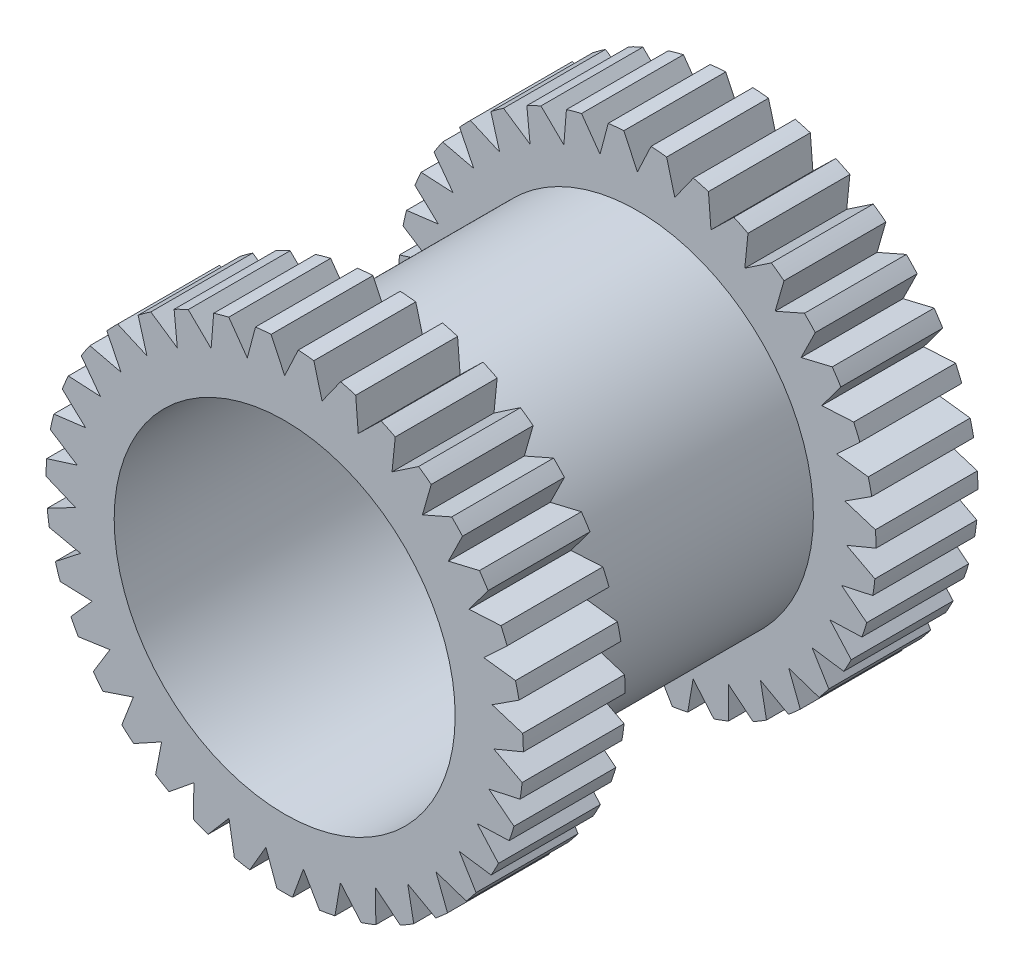
SolidWorks part; units mm, degrees
material "Brass"
ref_plane "Front Plane" through (0, 0, 0) normal (0, 0, 1) x (1, 0, 0)
ref_plane "Top Plane" through (0, 0, 0) normal (0, 1, 0) x (1, 0, 0)
ref_plane "Right Plane" through (0, 0, 0) normal (1, 0, 0) x (0, 0, -1)
sketch "Sketch1" plane through (0, 0, 0) normal (0, 1, 0) x (1, 0, 0)
  line L0 (2.1, 2) -> (0, 2)
  line L1 (0, 2) -> (0, -2)
  line L2 (0, -2) -> (2.1, -2)
  line L3 (2.1, -2) -> (2.1, -1.1034)
  line L4 (2.1, -1.1034) -> (1.5483, -1.1034)
  line L5 (1.5483, -1.1034) -> (1.5483, 1.1034)
  line L6 (1.5483, 1.1034) -> (2.1, 1.1034)
  line L7 (2.1, 1.1034) -> (2.1, 2)
  line L8 (0, 2) -> (0, -2) construction
  dimension "D1" = 4
  dimension "D2" = 2.1
revolve "Revolve1" add sketch "Sketch1" angle 360 about L8 reverse direction yes
sketch "Sketch2" plane through (0, 0, -2) normal (0, 0, -1) x (-1, 0, 0)
  line L0 (0.673, -1.9892) -> (0.49, -1.7755)
  line L1 (0.49, -1.7755) -> (0.4425, -2.0528)
  arc A0 (0.4425, -2.0528) -> (0.673, -1.9892) centre (0, 0) ccw
extrude "Cut-Extrude1" cut sketch "Sketch2" against normal blind 0.65
sketch "Sketch3" plane through (0, 0, -2) normal (0, 0, -1) x (-1, 0, 0)
  line L0 (0.307, -2.0774) -> (0.1651, -1.8345)
  line L1 (0.1651, -1.8345) -> (0.0689, -2.0989)
  arc A0 (0.0689, -2.0989) -> (0.307, -2.0774) centre (0, 0) ccw
extrude "Cut-Extrude2" cut sketch "Sketch3" against normal blind 0.65
sketch "Sketch4" plane through (0, 0, -2) normal (0, 0, -1) x (-1, 0, 0)
  line L0 (-0.0689, -2.0989) -> (-0.1651, -1.8345)
  line L1 (-0.1651, -1.8345) -> (-0.307, -2.0774)
  arc A0 (-0.307, -2.0774) -> (-0.0689, -2.0989) centre (0, 0) ccw
extrude "Cut-Extrude3" cut sketch "Sketch4" against normal blind 0.65
sketch "Sketch5" plane through (0, 0, -2) normal (0, 0, -1) x (-1, 0, 0)
  line L0 (-0.4425, -2.0528) -> (-0.49, -1.7755)
  line L1 (-0.49, -1.7755) -> (-0.673, -1.9892)
  arc A0 (-0.673, -1.9892) -> (-0.4425, -2.0528) centre (0, 0) ccw
extrude "Cut-Extrude4" cut sketch "Sketch5" against normal blind 0.65
sketch "Sketch6" plane through (0, 0, -2) normal (0, 0, -1) x (-1, 0, 0)
  line L0 (-0.802, -1.9408) -> (-0.7992, -1.6595)
  line L1 (-0.7992, -1.6595) -> (-1.0174, -1.8371)
  arc A0 (-1.0174, -1.8371) -> (-0.802, -1.9408) centre (0, 0) ccw
extrude "Cut-Extrude5" cut sketch "Sketch6" against normal blind 0.65
sketch "Sketch7" plane through (0, 0, -2) normal (0, 0, -1) x (-1, 0, 0)
  line L0 (-1.1356, -1.7664) -> (-1.0826, -1.4901)
  line L1 (-1.0826, -1.4901) -> (-1.3291, -1.6259)
  arc A0 (-1.3291, -1.6259) -> (-1.1356, -1.7664) centre (0, 0) ccw
extrude "Cut-Extrude6" cut sketch "Sketch7" against normal blind 0.65
sketch "Sketch8" plane through (0, 0, -2) normal (0, 0, -1) x (-1, 0, 0)
  line L0 (-1.4328, -1.5353) -> (-1.3313, -1.2729)
  line L1 (-1.3313, -1.2729) -> (-1.598, -1.3625)
  arc A0 (-1.598, -1.3625) -> (-1.4328, -1.5353) centre (0, 0) ccw
extrude "Cut-Extrude7" cut sketch "Sketch8" against normal blind 0.65
sketch "Sketch9" plane through (0, 0, -2) normal (0, 0, -1) x (-1, 0, 0)
  line L0 (-1.6839, -1.2548) -> (-1.5372, -1.0147)
  line L1 (-1.5372, -1.0147) -> (-1.8156, -1.0552)
  arc A0 (-1.8156, -1.0552) -> (-1.6839, -1.2548) centre (0, 0) ccw
extrude "Cut-Extrude8" cut sketch "Sketch9" against normal blind 0.65
sketch "Sketch10" plane through (0, 0, -2) normal (0, 0, -1) x (-1, 0, 0)
  line L0 (-1.8809, -0.9339) -> (-1.6937, -0.7239)
  line L1 (-1.6937, -0.7239) -> (-1.9749, -0.7141)
  arc A0 (-1.9749, -0.7141) -> (-1.8809, -0.9339) centre (0, 0) ccw
extrude "Cut-Extrude9" cut sketch "Sketch10" against normal blind 0.65
sketch "Sketch11" plane through (0, 0, -2) normal (0, 0, -1) x (-1, 0, 0)
  line L0 (-2.0174, -0.5831) -> (-1.7957, -0.4099)
  line L1 (-1.7957, -0.4099) -> (-2.0706, -0.35)
  arc A0 (-2.0706, -0.35) -> (-2.0174, -0.5831) centre (0, 0) ccw
extrude "Cut-Extrude10" cut sketch "Sketch11" against normal blind 0.65
sketch "Sketch12" plane through (0, 0, -2) normal (0, 0, -1) x (-1, 0, 0)
  line L0 (-2.0891, -0.2135) -> (-1.84, -0.0826)
  line L1 (-1.84, -0.0826) -> (-2.0998, 0.0254)
  arc A0 (-2.0998, 0.0254) -> (-2.0891, -0.2135) centre (0, 0) ccw
extrude "Cut-Extrude11" cut sketch "Sketch12" against normal blind 0.65
sketch "Sketch13" plane through (0, 0, -2) normal (0, 0, -1) x (-1, 0, 0)
  line L0 (-2.0937, 0.163) -> (-1.8252, 0.2472)
  line L1 (-1.8252, 0.2472) -> (-2.0616, 0.3999)
  arc A0 (-2.0616, 0.3999) -> (-2.0937, 0.163) centre (0, 0) ccw
extrude "Cut-Extrude12" cut sketch "Sketch13" against normal blind 0.65
sketch "Sketch14" plane through (0, 0, -2) normal (0, 0, -1) x (-1, 0, 0)
  line L0 (-2.0309, 0.5342) -> (-1.7517, 0.5692)
  line L1 (-1.7517, 0.5692) -> (-1.957, 0.7616)
  arc A0 (-1.957, 0.7616) -> (-2.0309, 0.5342) centre (0, 0) ccw
extrude "Cut-Extrude13" cut sketch "Sketch14" against normal blind 0.65
sketch "Sketch15" plane through (0, 0, -2) normal (0, 0, -1) x (-1, 0, 0)
  line L0 (-1.9029, 0.8882) -> (-1.622, 0.8728)
  line L1 (-1.622, 0.8728) -> (-1.7896, 1.0988)
  arc A0 (-1.7896, 1.0988) -> (-1.9029, 0.8882) centre (0, 0) ccw
extrude "Cut-Extrude14" cut sketch "Sketch15" against normal blind 0.65
sketch "Sketch16" plane through (0, 0, -2) normal (0, 0, -1) x (-1, 0, 0)
  line L0 (-1.7137, 1.2137) -> (-1.44, 1.1484)
  line L1 (-1.44, 1.1484) -> (-1.5646, 1.4007)
  arc A0 (-1.5646, 1.4007) -> (-1.7137, 1.2137) centre (0, 0) ccw
extrude "Cut-Extrude15" cut sketch "Sketch16" against normal blind 0.65
sketch "Sketch17" plane through (0, 0, -2) normal (0, 0, -1) x (-1, 0, 0)
  line L0 (-1.4695, 1.5002) -> (-1.2118, 1.3871)
  line L1 (-1.2118, 1.3871) -> (-1.2894, 1.6575)
  arc A0 (-1.2894, 1.6575) -> (-1.4695, 1.5002) centre (0, 0) ccw
extrude "Cut-Extrude16" cut sketch "Sketch17" against normal blind 0.65
sketch "Sketch18" plane through (0, 0, -2) normal (0, 0, -1) x (-1, 0, 0)
  line L0 (-1.178, 1.7385) -> (-0.9447, 1.5812)
  line L1 (-0.9447, 1.5812) -> (-0.9727, 1.8611)
  arc A0 (-0.9727, 1.8611) -> (-1.178, 1.7385) centre (0, 0) ccw
extrude "Cut-Extrude17" cut sketch "Sketch18" against normal blind 0.65
sketch "Sketch19" plane through (0, 0, -2) normal (0, 0, -1) x (-1, 0, 0)
  line L0 (-0.8486, 1.9209) -> (-0.6472, 1.7244)
  line L1 (-0.6472, 1.7244) -> (-0.6248, 2.0049)
  arc A0 (-0.6248, 2.0049) -> (-0.8486, 1.9209) centre (0, 0) ccw
extrude "Cut-Extrude18" cut sketch "Sketch19" against normal blind 0.65
sketch "Sketch20" plane through (0, 0, -2) normal (0, 0, -1) x (-1, 0, 0)
  line L0 (-0.492, 2.0416) -> (-0.3289, 1.8123)
  line L1 (-0.3289, 1.8123) -> (-0.2567, 2.0842)
  arc A0 (-0.2567, 2.0842) -> (-0.492, 2.0416) centre (0, 0) ccw
extrude "Cut-Extrude19" cut sketch "Sketch20" against normal blind 0.65
sketch "Sketch21" plane through (0, 0, -2) normal (0, 0, -1) x (-1, 0, 0)
  line L0 (-0.1195, 2.0966) -> (0, 1.8419)
  line L1 (0, 1.8419) -> (0.1195, 2.0966)
  arc A0 (0.1195, 2.0966) -> (-0.1195, 2.0966) centre (0, 0) ccw
extrude "Cut-Extrude20" cut sketch "Sketch21" against normal blind 0.65
sketch "Sketch22" plane through (0, 0, -2) normal (0, 0, -1) x (-1, 0, 0)
  line L0 (0.2567, 2.0842) -> (0.3289, 1.8123)
  line L1 (0.3289, 1.8123) -> (0.492, 2.0416)
  arc A0 (0.492, 2.0416) -> (0.2567, 2.0842) centre (0, 0) ccw
extrude "Cut-Extrude21" cut sketch "Sketch22" against normal blind 0.65
sketch "Sketch23" plane through (0, 0, -2) normal (0, 0, -1) x (-1, 0, 0)
  line L0 (0.6248, 2.0049) -> (0.6472, 1.7244)
  line L1 (0.6472, 1.7244) -> (0.8486, 1.9209)
  arc A0 (0.8486, 1.9209) -> (0.6248, 2.0049) centre (0, 0) ccw
extrude "Cut-Extrude22" cut sketch "Sketch23" against normal blind 0.65
sketch "Sketch24" plane through (0, 0, -2) normal (0, 0, -1) x (-1, 0, 0)
  line L0 (0.9727, 1.8611) -> (0.9447, 1.5812)
  line L1 (0.9447, 1.5812) -> (1.178, 1.7385)
  arc A0 (1.178, 1.7385) -> (0.9727, 1.8611) centre (0, 0) ccw
extrude "Cut-Extrude23" cut sketch "Sketch24" against normal blind 0.65
sketch "Sketch25" plane through (0, 0, -2) normal (0, 0, -1) x (-1, 0, 0)
  line L0 (1.2894, 1.6575) -> (1.2118, 1.3871)
  line L1 (1.2118, 1.3871) -> (1.4695, 1.5002)
  arc A0 (1.4695, 1.5002) -> (1.2894, 1.6575) centre (0, 0) ccw
extrude "Cut-Extrude24" cut sketch "Sketch25" against normal blind 0.65
sketch "Sketch26" plane through (0, 0, -2) normal (0, 0, -1) x (-1, 0, 0)
  line L0 (1.5646, 1.4007) -> (1.44, 1.1484)
  line L1 (1.44, 1.1484) -> (1.7137, 1.2137)
  arc A0 (1.7137, 1.2137) -> (1.5646, 1.4007) centre (0, 0) ccw
extrude "Cut-Extrude25" cut sketch "Sketch26" against normal blind 0.65
sketch "Sketch27" plane through (0, 0, -2) normal (0, 0, -1) x (-1, 0, 0)
  line L0 (1.7896, 1.0988) -> (1.622, 0.8728)
  line L1 (1.622, 0.8728) -> (1.9029, 0.8882)
  arc A0 (1.9029, 0.8882) -> (1.7896, 1.0988) centre (0, 0) ccw
extrude "Cut-Extrude26" cut sketch "Sketch27" against normal blind 0.65
sketch "Sketch28" plane through (0, 0, -2) normal (0, 0, -1) x (-1, 0, 0)
  line L0 (1.957, 0.7616) -> (1.7517, 0.5692)
  line L1 (1.7517, 0.5692) -> (2.0309, 0.5342)
  arc A0 (2.0309, 0.5342) -> (1.957, 0.7616) centre (0, 0) ccw
extrude "Cut-Extrude27" cut sketch "Sketch28" against normal blind 0.65
sketch "Sketch29" plane through (0, 0, -2) normal (0, 0, -1) x (-1, 0, 0)
  line L0 (2.0616, 0.3999) -> (1.8252, 0.2472)
  line L1 (1.8252, 0.2472) -> (2.0937, 0.163)
  arc A0 (2.0937, 0.163) -> (2.0616, 0.3999) centre (0, 0) ccw
extrude "Cut-Extrude28" cut sketch "Sketch29" against normal blind 0.65
sketch "Sketch30" plane through (0, 0, -2) normal (0, 0, -1) x (-1, 0, 0)
  line L0 (2.0998, 0.0254) -> (1.84, -0.0826)
  line L1 (1.84, -0.0826) -> (2.0891, -0.2135)
  arc A0 (2.0891, -0.2135) -> (2.0998, 0.0254) centre (0, 0) ccw
extrude "Cut-Extrude29" cut sketch "Sketch30" against normal blind 0.65
sketch "Sketch31" plane through (0, 0, -2) normal (0, 0, -1) x (-1, 0, 0)
  line L0 (2.0706, -0.35) -> (1.7957, -0.4099)
  line L1 (1.7957, -0.4099) -> (2.0174, -0.5831)
  arc A0 (2.0174, -0.5831) -> (2.0706, -0.35) centre (0, 0) ccw
extrude "Cut-Extrude30" cut sketch "Sketch31" against normal blind 0.65
sketch "Sketch32" plane through (0, 0, -2) normal (0, 0, -1) x (-1, 0, 0)
  line L0 (1.9749, -0.7141) -> (1.6937, -0.7239)
  line L1 (1.6937, -0.7239) -> (1.8809, -0.9339)
  arc A0 (1.8809, -0.9339) -> (1.9749, -0.7141) centre (0, 0) ccw
extrude "Cut-Extrude31" cut sketch "Sketch32" against normal blind 0.65
sketch "Sketch33" plane through (0, 0, -2) normal (0, 0, -1) x (-1, 0, 0)
  line L0 (1.8156, -1.0552) -> (1.5372, -1.0147)
  line L1 (1.5372, -1.0147) -> (1.6839, -1.2548)
  arc A0 (1.6839, -1.2548) -> (1.8156, -1.0552) centre (0, 0) ccw
extrude "Cut-Extrude32" cut sketch "Sketch33" against normal blind 0.65
sketch "Sketch34" plane through (0, 0, -2) normal (0, 0, -1) x (-1, 0, 0)
  line L0 (1.598, -1.3625) -> (1.3313, -1.2729)
  line L1 (1.3313, -1.2729) -> (1.4328, -1.5353)
  arc A0 (1.4328, -1.5353) -> (1.598, -1.3625) centre (0, 0) ccw
extrude "Cut-Extrude33" cut sketch "Sketch34" against normal blind 0.65
sketch "Sketch35" plane through (0, 0, -2) normal (0, 0, -1) x (-1, 0, 0)
  line L0 (1.3291, -1.6259) -> (1.0826, -1.4901)
  line L1 (1.0826, -1.4901) -> (1.1356, -1.7664)
  arc A0 (1.1356, -1.7664) -> (1.3291, -1.6259) centre (0, 0) ccw
extrude "Cut-Extrude34" cut sketch "Sketch35" against normal blind 0.65
sketch "Sketch36" plane through (0, 0, -2) normal (0, 0, -1) x (-1, 0, 0)
  line L0 (1.0174, -1.8371) -> (0.7992, -1.6595)
  line L1 (0.7992, -1.6595) -> (0.802, -1.9408)
  arc A0 (0.802, -1.9408) -> (1.0174, -1.8371) centre (0, 0) ccw
extrude "Cut-Extrude35" cut sketch "Sketch36" against normal blind 0.65
sketch "Sketch37" plane through (0, 0, 2) normal (0, 0, 1) x (1, 0, 0)
  line L0 (-0.4425, -2.0528) -> (-0.49, -1.7755)
  line L1 (-0.49, -1.7755) -> (-0.673, -1.9892)
  arc A0 (-0.673, -1.9892) -> (-0.4425, -2.0528) centre (0, 0) ccw
extrude "Cut-Extrude36" cut sketch "Sketch37" against normal blind 0.65
sketch "Sketch38" plane through (0, 0, 2) normal (0, 0, 1) x (1, 0, 0)
  line L0 (-0.802, -1.9408) -> (-0.7992, -1.6595)
  line L1 (-0.7992, -1.6595) -> (-1.0174, -1.8371)
  arc A0 (-1.0174, -1.8371) -> (-0.802, -1.9408) centre (0, 0) ccw
extrude "Cut-Extrude37" cut sketch "Sketch38" against normal blind 0.65
sketch "Sketch39" plane through (0, 0, 2) normal (0, 0, 1) x (1, 0, 0)
  line L0 (-1.1356, -1.7664) -> (-1.0826, -1.4901)
  line L1 (-1.0826, -1.4901) -> (-1.3291, -1.6259)
  arc A0 (-1.3291, -1.6259) -> (-1.1356, -1.7664) centre (0, 0) ccw
extrude "Cut-Extrude38" cut sketch "Sketch39" against normal blind 0.65
sketch "Sketch40" plane through (0, 0, 2) normal (0, 0, 1) x (1, 0, 0)
  line L0 (-1.4328, -1.5353) -> (-1.3313, -1.2729)
  line L1 (-1.3313, -1.2729) -> (-1.598, -1.3625)
  arc A0 (-1.598, -1.3625) -> (-1.4328, -1.5353) centre (0, 0) ccw
extrude "Cut-Extrude39" cut sketch "Sketch40" against normal blind 0.65
sketch "Sketch41" plane through (0, 0, 2) normal (0, 0, 1) x (1, 0, 0)
  line L0 (-1.6839, -1.2548) -> (-1.5372, -1.0147)
  line L1 (-1.5372, -1.0147) -> (-1.8156, -1.0552)
  arc A0 (-1.8156, -1.0552) -> (-1.6839, -1.2548) centre (0, 0) ccw
extrude "Cut-Extrude40" cut sketch "Sketch41" against normal blind 0.65
sketch "Sketch42" plane through (0, 0, 2) normal (0, 0, 1) x (1, 0, 0)
  line L0 (-1.8809, -0.9339) -> (-1.6937, -0.7239)
  line L1 (-1.6937, -0.7239) -> (-1.9749, -0.7141)
  arc A0 (-1.9749, -0.7141) -> (-1.8809, -0.9339) centre (0, 0) ccw
extrude "Cut-Extrude41" cut sketch "Sketch42" against normal blind 0.65
sketch "Sketch43" plane through (0, 0, 2) normal (0, 0, 1) x (1, 0, 0)
  line L0 (-2.0174, -0.5831) -> (-1.7957, -0.4099)
  line L1 (-1.7957, -0.4099) -> (-2.0706, -0.35)
  arc A0 (-2.0706, -0.35) -> (-2.0174, -0.5831) centre (0, 0) ccw
extrude "Cut-Extrude42" cut sketch "Sketch43" against normal blind 0.65
sketch "Sketch44" plane through (0, 0, 2) normal (0, 0, 1) x (1, 0, 0)
  line L0 (-2.0891, -0.2135) -> (-1.84, -0.0826)
  line L1 (-1.84, -0.0826) -> (-2.0998, 0.0254)
  arc A0 (-2.0998, 0.0254) -> (-2.0891, -0.2135) centre (0, 0) ccw
extrude "Cut-Extrude43" cut sketch "Sketch44" against normal blind 0.65
sketch "Sketch45" plane through (0, 0, 2) normal (0, 0, 1) x (1, 0, 0)
  line L0 (-2.0937, 0.163) -> (-1.8252, 0.2472)
  line L1 (-1.8252, 0.2472) -> (-2.0616, 0.3999)
  arc A0 (-2.0616, 0.3999) -> (-2.0937, 0.163) centre (0, 0) ccw
extrude "Cut-Extrude44" cut sketch "Sketch45" against normal blind 0.65
sketch "Sketch46" plane through (0, 0, 2) normal (0, 0, 1) x (1, 0, 0)
  line L0 (-2.0309, 0.5342) -> (-1.7517, 0.5692)
  line L1 (-1.7517, 0.5692) -> (-1.957, 0.7616)
  arc A0 (-1.957, 0.7616) -> (-2.0309, 0.5342) centre (0, 0) ccw
extrude "Cut-Extrude45" cut sketch "Sketch46" against normal blind 0.65
sketch "Sketch47" plane through (0, 0, 2) normal (0, 0, 1) x (1, 0, 0)
  line L0 (-1.9029, 0.8882) -> (-1.622, 0.8728)
  line L1 (-1.622, 0.8728) -> (-1.7896, 1.0988)
  arc A0 (-1.7896, 1.0988) -> (-1.9029, 0.8882) centre (0, 0) ccw
extrude "Cut-Extrude46" cut sketch "Sketch47" against normal blind 0.65
sketch "Sketch48" plane through (0, 0, 2) normal (0, 0, 1) x (1, 0, 0)
  line L0 (-1.7137, 1.2137) -> (-1.44, 1.1484)
  line L1 (-1.44, 1.1484) -> (-1.5646, 1.4007)
  arc A0 (-1.5646, 1.4007) -> (-1.7137, 1.2137) centre (0, 0) ccw
extrude "Cut-Extrude47" cut sketch "Sketch48" against normal blind 0.65
sketch "Sketch49" plane through (0, 0, 2) normal (0, 0, 1) x (1, 0, 0)
  line L0 (-1.4695, 1.5002) -> (-1.2118, 1.3871)
  line L1 (-1.2118, 1.3871) -> (-1.2894, 1.6575)
  arc A0 (-1.2894, 1.6575) -> (-1.4695, 1.5002) centre (0, 0) ccw
extrude "Cut-Extrude48" cut sketch "Sketch49" against normal blind 0.65
sketch "Sketch50" plane through (0, 0, 2) normal (0, 0, 1) x (1, 0, 0)
  line L0 (-1.178, 1.7385) -> (-0.9447, 1.5812)
  line L1 (-0.9447, 1.5812) -> (-0.9727, 1.8611)
  arc A0 (-0.9727, 1.8611) -> (-1.178, 1.7385) centre (0, 0) ccw
extrude "Cut-Extrude49" cut sketch "Sketch50" against normal blind 0.65
sketch "Sketch51" plane through (0, 0, 2) normal (0, 0, 1) x (1, 0, 0)
  line L0 (-0.8486, 1.9209) -> (-0.6472, 1.7244)
  line L1 (-0.6472, 1.7244) -> (-0.6248, 2.0049)
  arc A0 (-0.6248, 2.0049) -> (-0.8486, 1.9209) centre (0, 0) ccw
extrude "Cut-Extrude50" cut sketch "Sketch51" against normal blind 0.65
sketch "Sketch52" plane through (0, 0, 2) normal (0, 0, 1) x (1, 0, 0)
  line L0 (-0.492, 2.0416) -> (-0.3289, 1.8123)
  line L1 (-0.3289, 1.8123) -> (-0.2567, 2.0842)
  arc A0 (-0.2567, 2.0842) -> (-0.492, 2.0416) centre (0, 0) ccw
extrude "Cut-Extrude51" cut sketch "Sketch52" against normal blind 0.65
sketch "Sketch53" plane through (0, 0, 2) normal (0, 0, 1) x (1, 0, 0)
  line L0 (-0.1195, 2.0966) -> (0, 1.8419)
  line L1 (0, 1.8419) -> (0.1195, 2.0966)
  arc A0 (0.1195, 2.0966) -> (-0.1195, 2.0966) centre (0, 0) ccw
extrude "Cut-Extrude52" cut sketch "Sketch53" against normal blind 0.65
sketch "Sketch54" plane through (0, 0, 2) normal (0, 0, 1) x (1, 0, 0)
  line L0 (0.2567, 2.0842) -> (0.3289, 1.8123)
  line L1 (0.3289, 1.8123) -> (0.492, 2.0416)
  arc A0 (0.492, 2.0416) -> (0.2567, 2.0842) centre (0, 0) ccw
extrude "Cut-Extrude53" cut sketch "Sketch54" against normal blind 0.65
sketch "Sketch55" plane through (0, 0, 2) normal (0, 0, 1) x (1, 0, 0)
  line L0 (0.6248, 2.0049) -> (0.6472, 1.7244)
  line L1 (0.6472, 1.7244) -> (0.8486, 1.9209)
  arc A0 (0.8486, 1.9209) -> (0.6248, 2.0049) centre (0, 0) ccw
extrude "Cut-Extrude54" cut sketch "Sketch55" against normal blind 0.65
sketch "Sketch56" plane through (0, 0, 2) normal (0, 0, 1) x (1, 0, 0)
  line L0 (0.9727, 1.8611) -> (0.9447, 1.5812)
  line L1 (0.9447, 1.5812) -> (1.178, 1.7385)
  arc A0 (1.178, 1.7385) -> (0.9727, 1.8611) centre (0, 0) ccw
extrude "Cut-Extrude55" cut sketch "Sketch56" against normal blind 0.65
sketch "Sketch57" plane through (0, 0, 2) normal (0, 0, 1) x (1, 0, 0)
  line L0 (1.2894, 1.6575) -> (1.2118, 1.3871)
  line L1 (1.2118, 1.3871) -> (1.4695, 1.5002)
  arc A0 (1.4695, 1.5002) -> (1.2894, 1.6575) centre (0, 0) ccw
extrude "Cut-Extrude56" cut sketch "Sketch57" against normal blind 0.65
sketch "Sketch58" plane through (0, 0, 2) normal (0, 0, 1) x (1, 0, 0)
  line L0 (1.5646, 1.4007) -> (1.44, 1.1484)
  line L1 (1.44, 1.1484) -> (1.7137, 1.2137)
  arc A0 (1.7137, 1.2137) -> (1.5646, 1.4007) centre (0, 0) ccw
extrude "Cut-Extrude57" cut sketch "Sketch58" against normal blind 0.65
sketch "Sketch59" plane through (0, 0, 2) normal (0, 0, 1) x (1, 0, 0)
  line L0 (1.7896, 1.0988) -> (1.622, 0.8728)
  line L1 (1.622, 0.8728) -> (1.9029, 0.8882)
  arc A0 (1.9029, 0.8882) -> (1.7896, 1.0988) centre (0, 0) ccw
extrude "Cut-Extrude58" cut sketch "Sketch59" against normal blind 0.65
sketch "Sketch60" plane through (0, 0, 2) normal (0, 0, 1) x (1, 0, 0)
  line L0 (1.957, 0.7616) -> (1.7517, 0.5692)
  line L1 (1.7517, 0.5692) -> (2.0309, 0.5342)
  arc A0 (2.0309, 0.5342) -> (1.957, 0.7616) centre (0, 0) ccw
extrude "Cut-Extrude59" cut sketch "Sketch60" against normal blind 0.65
sketch "Sketch61" plane through (0, 0, 2) normal (0, 0, 1) x (1, 0, 0)
  line L0 (2.0616, 0.3999) -> (1.8252, 0.2472)
  line L1 (1.8252, 0.2472) -> (2.0937, 0.163)
  arc A0 (2.0937, 0.163) -> (2.0616, 0.3999) centre (0, 0) ccw
extrude "Cut-Extrude60" cut sketch "Sketch61" against normal blind 0.65
sketch "Sketch62" plane through (0, 0, 2) normal (0, 0, 1) x (1, 0, 0)
  line L0 (2.0998, 0.0254) -> (1.84, -0.0826)
  line L1 (1.84, -0.0826) -> (2.0891, -0.2135)
  arc A0 (2.0891, -0.2135) -> (2.0998, 0.0254) centre (0, 0) ccw
extrude "Cut-Extrude61" cut sketch "Sketch62" against normal blind 0.65
sketch "Sketch63" plane through (0, 0, 2) normal (0, 0, 1) x (1, 0, 0)
  line L0 (2.0706, -0.35) -> (1.7957, -0.4099)
  line L1 (1.7957, -0.4099) -> (2.0174, -0.5831)
  arc A0 (2.0174, -0.5831) -> (2.0706, -0.35) centre (0, 0) ccw
extrude "Cut-Extrude62" cut sketch "Sketch63" against normal blind 0.65
sketch "Sketch64" plane through (0, 0, 2) normal (0, 0, 1) x (1, 0, 0)
  line L0 (1.9749, -0.7141) -> (1.6937, -0.7239)
  line L1 (1.6937, -0.7239) -> (1.8809, -0.9339)
  arc A0 (1.8809, -0.9339) -> (1.9749, -0.7141) centre (0, 0) ccw
extrude "Cut-Extrude63" cut sketch "Sketch64" against normal blind 0.65
sketch "Sketch65" plane through (0, 0, 2) normal (0, 0, 1) x (1, 0, 0)
  line L0 (1.8156, -1.0552) -> (1.5372, -1.0147)
  line L1 (1.5372, -1.0147) -> (1.6839, -1.2548)
  arc A0 (1.6839, -1.2548) -> (1.8156, -1.0552) centre (0, 0) ccw
extrude "Cut-Extrude64" cut sketch "Sketch65" against normal blind 0.65
sketch "Sketch66" plane through (0, 0, 2) normal (0, 0, 1) x (1, 0, 0)
  line L0 (1.598, -1.3625) -> (1.3313, -1.2729)
  line L1 (1.3313, -1.2729) -> (1.4328, -1.5353)
  arc A0 (1.4328, -1.5353) -> (1.598, -1.3625) centre (0, 0) ccw
extrude "Cut-Extrude65" cut sketch "Sketch66" against normal blind 0.65
sketch "Sketch67" plane through (0, 0, 2) normal (0, 0, 1) x (1, 0, 0)
  line L0 (1.3291, -1.6259) -> (1.0826, -1.4901)
  line L1 (1.0826, -1.4901) -> (1.1356, -1.7664)
  arc A0 (1.1356, -1.7664) -> (1.3291, -1.6259) centre (0, 0) ccw
extrude "Cut-Extrude66" cut sketch "Sketch67" against normal blind 0.65
sketch "Sketch68" plane through (0, 0, 2) normal (0, 0, 1) x (1, 0, 0)
  line L0 (1.0174, -1.8371) -> (0.7992, -1.6595)
  line L1 (0.7992, -1.6595) -> (0.802, -1.9408)
  arc A0 (0.802, -1.9408) -> (1.0174, -1.8371) centre (0, 0) ccw
extrude "Cut-Extrude67" cut sketch "Sketch68" against normal blind 0.65
sketch "Sketch69" plane through (0, 0, 2) normal (0, 0, 1) x (1, 0, 0)
  line L0 (0.673, -1.9892) -> (0.49, -1.7755)
  line L1 (0.49, -1.7755) -> (0.4425, -2.0528)
  arc A0 (0.4425, -2.0528) -> (0.673, -1.9892) centre (0, 0) ccw
extrude "Cut-Extrude68" cut sketch "Sketch69" against normal blind 0.65
sketch "Sketch70" plane through (0, 0, 2) normal (0, 0, 1) x (1, 0, 0)
  line L0 (0.307, -2.0774) -> (0.1651, -1.8345)
  line L1 (0.1651, -1.8345) -> (0.0689, -2.0989)
  arc A0 (0.0689, -2.0989) -> (0.307, -2.0774) centre (0, 0) ccw
extrude "Cut-Extrude69" cut sketch "Sketch70" against normal blind 0.65
sketch "Sketch71" plane through (0, 0, 2) normal (0, 0, 1) x (1, 0, 0)
  line L0 (-0.0689, -2.0989) -> (-0.1651, -1.8345)
  line L1 (-0.1651, -1.8345) -> (-0.307, -2.0774)
  arc A0 (-0.307, -2.0774) -> (-0.0689, -2.0989) centre (0, 0) ccw
extrude "Cut-Extrude70" cut sketch "Sketch71" against normal blind 0.65
hole_wizard "Ø3.0 (3) Diameter Hole1" positions "Sketch73" profile "Sketch72" hole size "Ø3.0" standard "ANSI Metric"
sketch "Sketch73" plane through (0, 0, -2) normal (0, 0, -1) x (-1, 0, 0)
  point P0 (0, 0)
sketch "Sketch72" plane through (0, 0, -2) normal (1, 0, 0) x (0, 1, 0)
  line L0 (0, 0) -> (0, 4)
  line L1 (0, 4) -> (1.5, 4)
  line L2 (1.5, 4) -> (1.5, 0)
  line L5 (1.5, 0) -> (0, 0)
  line L11 (0, -6.35) -> (0, 107.95) construction
  dimension "Thru Hole Dia." = 3
  dimension "Thru Hole Depth" = 4
sketch "Sketch74" plane through (0, 0, -1.35) normal (0, 0, -1) x (-1, 0, 0)
  line L0 (0.49, -1.7755) -> (0.673, -1.9892)
  line L1 (0.673, -1.9892) -> (0.5941, -2.1078)
  line L2 (0.5941, -2.1078) -> (0.4425, -2.0528)
  line L3 (0.4425, -2.0528) -> (0.49, -1.7755)
  line L4 (0.0689, -2.0989) -> (0.1651, -1.8345)
  line L5 (0.1651, -1.8345) -> (0.307, -2.0774)
  line L6 (0.307, -2.0774) -> (0.2082, -2.18)
  line L7 (0.2082, -2.18) -> (0.0689, -2.0989)
  line L8 (-0.307, -2.0774) -> (-0.1651, -1.8345)
  line L9 (-0.1651, -1.8345) -> (-0.0689, -2.0989)
  line L10 (-0.0689, -2.0989) -> (-0.1844, -2.1822)
  line L11 (-0.1844, -2.1822) -> (-0.307, -2.0774)
  line L12 (-0.673, -1.9892) -> (-0.49, -1.7755)
  line L13 (-0.49, -1.7755) -> (-0.4425, -2.0528)
  line L14 (-0.4425, -2.0528) -> (-0.5711, -2.1142)
  line L15 (-0.5711, -2.1142) -> (-0.673, -1.9892)
  line L16 (-1.0174, -1.8371) -> (-0.7992, -1.6595)
  line L17 (-0.7992, -1.6595) -> (-0.802, -1.9408)
  line L18 (-0.802, -1.9408) -> (-0.9394, -1.9782)
  line L19 (-0.9394, -1.9782) -> (-1.0174, -1.8371)
  line L20 (-1.3291, -1.6259) -> (-1.0826, -1.4901)
  line L21 (-1.0826, -1.4901) -> (-1.1356, -1.7664)
  line L22 (-1.1356, -1.7664) -> (-1.2775, -1.7787)
  line L23 (-1.2775, -1.7787) -> (-1.3291, -1.6259)
  line L24 (-1.598, -1.3625) -> (-1.3313, -1.2729)
  line L25 (-1.3313, -1.2729) -> (-1.4328, -1.5353)
  line L26 (-1.4328, -1.5353) -> (-1.5746, -1.522)
  line L27 (-1.5746, -1.522) -> (-1.598, -1.3625)
  line L28 (-1.8156, -1.0552) -> (-1.5372, -1.0147)
  line L29 (-1.5372, -1.0147) -> (-1.6839, -1.2548)
  line L30 (-1.6839, -1.2548) -> (-1.821, -1.2164)
  line L31 (-1.821, -1.2164) -> (-1.8156, -1.0552)
  line L32 (-1.9749, -0.7141) -> (-1.6937, -0.7239)
  line L33 (-1.6937, -0.7239) -> (-1.8809, -0.9339)
  line L34 (-1.8809, -0.9339) -> (-2.009, -0.8717)
  line L35 (-2.009, -0.8717) -> (-1.9749, -0.7141)
  line L36 (-2.0706, -0.35) -> (-1.7957, -0.4099)
  line L37 (-1.7957, -0.4099) -> (-2.0174, -0.5831)
  line L38 (-2.0174, -0.5831) -> (-2.1323, -0.499)
  line L39 (-2.1323, -0.499) -> (-2.0706, -0.35)
  line L40 (-2.0998, 0.0254) -> (-1.84, -0.0826)
  line L41 (-1.84, -0.0826) -> (-2.0891, -0.2135)
  line L42 (-2.0891, -0.2135) -> (-2.1872, -0.1102)
  line L43 (-2.1872, -0.1102) -> (-2.0998, 0.0254)
  line L44 (-2.0616, 0.3999) -> (-1.8252, 0.2472)
  line L45 (-1.8252, 0.2472) -> (-2.0937, 0.163)
  line L46 (-2.0937, 0.163) -> (-2.1717, 0.2821)
  line L47 (-2.1717, 0.2821) -> (-2.0616, 0.3999)
  line L48 (-1.957, 0.7616) -> (-1.7517, 0.5692)
  line L49 (-1.7517, 0.5692) -> (-2.0309, 0.5342)
  line L50 (-2.0309, 0.5342) -> (-2.0864, 0.6653)
  line L51 (-2.0864, 0.6653) -> (-1.957, 0.7616)
  line L52 (-1.7896, 1.0988) -> (-1.622, 0.8728)
  line L53 (-1.622, 0.8728) -> (-1.9029, 0.8882)
  line L54 (-1.9029, 0.8882) -> (-1.9341, 1.0272)
  line L55 (-1.9341, 1.0272) -> (-1.7896, 1.0988)
  line L56 (-1.5646, 1.4007) -> (-1.44, 1.1484)
  line L57 (-1.44, 1.1484) -> (-1.7137, 1.2137)
  line L58 (-1.7137, 1.2137) -> (-1.7196, 1.356)
  line L59 (-1.7196, 1.356) -> (-1.5646, 1.4007)
  line L60 (-1.2894, 1.6575) -> (-1.2118, 1.3871)
  line L61 (-1.2118, 1.3871) -> (-1.4695, 1.5002)
  line L62 (-1.4695, 1.5002) -> (-1.4498, 1.6413)
  line L63 (-1.4498, 1.6413) -> (-1.2894, 1.6575)
  line L64 (-0.9727, 1.8611) -> (-0.9447, 1.5812)
  line L65 (-0.9447, 1.5812) -> (-1.178, 1.7385)
  line L66 (-1.178, 1.7385) -> (-1.1335, 1.8738)
  line L67 (-1.1335, 1.8738) -> (-0.9727, 1.8611)
  line L68 (-0.6248, 2.0049) -> (-0.6472, 1.7244)
  line L69 (-0.6472, 1.7244) -> (-0.8486, 1.9209)
  line L70 (-0.8486, 1.9209) -> (-0.7807, 2.0461)
  line L71 (-0.7807, 2.0461) -> (-0.6248, 2.0049)
  line L72 (-0.2567, 2.0842) -> (-0.3289, 1.8123)
  line L73 (-0.3289, 1.8123) -> (-0.492, 2.0416)
  line L74 (-0.492, 2.0416) -> (-0.4028, 2.1526)
  line L75 (-0.4028, 2.1526) -> (-0.2567, 2.0842)
  line L76 (0.1195, 2.0966) -> (0, 1.8419)
  line L77 (0, 1.8419) -> (-0.1195, 2.0966)
  line L78 (-0.1195, 2.0966) -> (-0.012, 2.1899)
  line L79 (-0.012, 2.1899) -> (0.1195, 2.0966)
  line L80 (0.492, 2.0416) -> (0.3289, 1.8123)
  line L81 (0.3289, 1.8123) -> (0.2567, 2.0842)
  line L82 (0.2567, 2.0842) -> (0.3792, 2.1569)
  line L83 (0.3792, 2.1569) -> (0.492, 2.0416)
  line L84 (0.8486, 1.9209) -> (0.6472, 1.7244)
  line L85 (0.6472, 1.7244) -> (0.6248, 2.0049)
  line L86 (0.6248, 2.0049) -> (0.7583, 2.0545)
  line L87 (0.7583, 2.0545) -> (0.8486, 1.9209)
  line L88 (1.178, 1.7385) -> (0.9447, 1.5812)
  line L89 (0.9447, 1.5812) -> (0.9727, 1.8611)
  line L90 (0.9727, 1.8611) -> (1.1129, 1.8861)
  line L91 (1.1129, 1.8861) -> (1.178, 1.7385)
  line L92 (1.4695, 1.5002) -> (1.2118, 1.3871)
  line L93 (1.2118, 1.3871) -> (1.2894, 1.6575)
  line L94 (1.2894, 1.6575) -> (1.4318, 1.657)
  line L95 (1.4318, 1.657) -> (1.4695, 1.5002)
  line L96 (1.7137, 1.2137) -> (1.44, 1.1484)
  line L97 (1.44, 1.1484) -> (1.5646, 1.4007)
  line L98 (1.5646, 1.4007) -> (1.7047, 1.3747)
  line L99 (1.7047, 1.3747) -> (1.7137, 1.2137)
  line L100 (1.9029, 0.8882) -> (1.622, 0.8728)
  line L101 (1.622, 0.8728) -> (1.7896, 1.0988)
  line L102 (1.7896, 1.0988) -> (1.9228, 1.0483)
  line L103 (1.9228, 1.0483) -> (1.9029, 0.8882)
  line L104 (2.0309, 0.5342) -> (1.7517, 0.5692)
  line L105 (1.7517, 0.5692) -> (1.957, 0.7616)
  line L106 (1.957, 0.7616) -> (2.079, 0.6881)
  line L107 (2.079, 0.6881) -> (2.0309, 0.5342)
  line L108 (2.0937, 0.163) -> (1.8252, 0.2472)
  line L109 (1.8252, 0.2472) -> (2.0616, 0.3999)
  line L110 (2.0616, 0.3999) -> (2.1685, 0.3058)
  line L111 (2.1685, 0.3058) -> (2.0937, 0.163)
  line L112 (2.0891, -0.2135) -> (1.84, -0.0826)
  line L113 (1.84, -0.0826) -> (2.0998, 0.0254)
  line L114 (2.0998, 0.0254) -> (2.1882, -0.0863)
  line L115 (2.1882, -0.0863) -> (2.0891, -0.2135)
  line L116 (2.0174, -0.5831) -> (1.7957, -0.4099)
  line L117 (1.7957, -0.4099) -> (2.0706, -0.35)
  line L118 (2.0706, -0.35) -> (2.1377, -0.4756)
  line L119 (2.1377, -0.4756) -> (2.0174, -0.5831)
  line L120 (1.8809, -0.9339) -> (1.6937, -0.7239)
  line L121 (1.6937, -0.7239) -> (1.9749, -0.7141)
  line L122 (1.9749, -0.7141) -> (2.0184, -0.8497)
  line L123 (2.0184, -0.8497) -> (1.8809, -0.9339)
  line L124 (1.6839, -1.2548) -> (1.5372, -1.0147)
  line L125 (1.5372, -1.0147) -> (1.8156, -1.0552)
  line L126 (1.8156, -1.0552) -> (1.8342, -1.1964)
  line L127 (1.8342, -1.1964) -> (1.6839, -1.2548)
  line L128 (1.4328, -1.5353) -> (1.3313, -1.2729)
  line L129 (1.3313, -1.2729) -> (1.598, -1.3625)
  line L130 (1.598, -1.3625) -> (1.5911, -1.5047)
  line L131 (1.5911, -1.5047) -> (1.4328, -1.5353)
  line L132 (1.1356, -1.7664) -> (1.0826, -1.4901)
  line L133 (1.0826, -1.4901) -> (1.3291, -1.6259)
  line L134 (1.3291, -1.6259) -> (1.2969, -1.7646)
  line L135 (1.2969, -1.7646) -> (1.1356, -1.7664)
  line L136 (0.802, -1.9408) -> (0.7992, -1.6595)
  line L137 (0.7992, -1.6595) -> (1.0174, -1.8371)
  line L138 (1.0174, -1.8371) -> (0.9609, -1.9678)
  line L139 (0.9609, -1.9678) -> (0.802, -1.9408)
  point P146 (0, 0)
  dimension "D1" = 35
extrude "Cut-Extrude71" cut sketch "Sketch74" against normal blind 10
